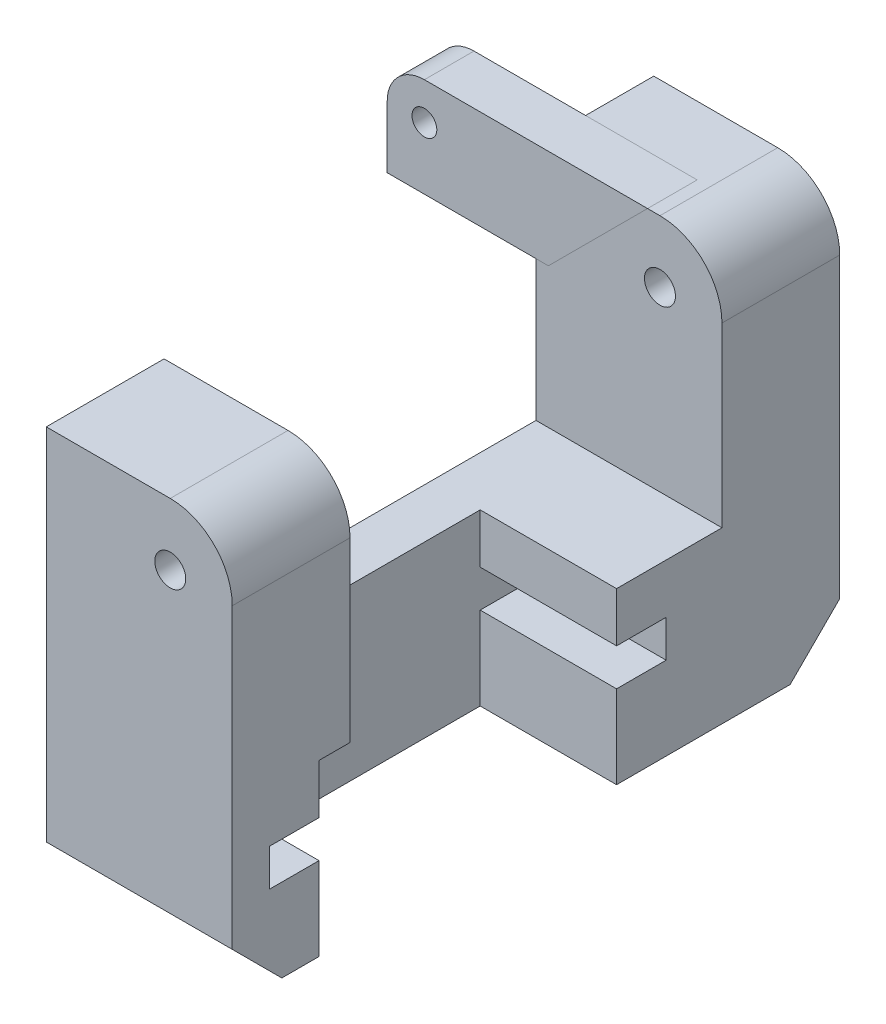
SolidWorks part; units mm, degrees
material "3D printed plastic"
ref_plane "Front Plane" through (0, 0, 0) normal (0, 0, 1) x (1, 0, 0)
ref_plane "Top Plane" through (0, 0, 0) normal (0, 1, 0) x (1, 0, 0)
ref_plane "Right Plane" through (0, 0, 0) normal (1, 0, 0) x (0, 0, -1)
sketch "Sketch1" plane through (0, 0, 0) normal (1, 0, 0) x (0, 0, -1)
  line L0 (0, 0) -> (0, -16.5) construction
  line L1 (-24.5, 16.5) -> (24.5, 16.5)
  line L2 (-24.5, 16.5) -> (-24.5, -16.5)
  line L3 (-24.5, -16.5) -> (24.5, -16.5)
  line L4 (24.5, 16.5) -> (24.5, -16.5)
  line L5 (0, 0) -> (0, 16.5) construction
  dimension "D1" = 49
  dimension "D2" = 33
extrude "Boss-Extrude1" add sketch "Sketch1" along normal mid plane 15
sketch "Sketch2" plane through (0, 0, 24.5) normal (0, 0, 1) x (1, 0, 0)
  line L0 (7.5, 16.5) -> (7.5, -16.5) construction
  line L1 (7.5, 16.5) -> (-7.5, 16.5) construction
  line L2 (2.5, 16.5) -> (7.5, 16.5)
  line L3 (7.5, 16.5) -> (7.5, 11.5)
  circle A0 centre (2.5, 11.5) radius 1.25
  arc A1 (7.5, 11.5) -> (2.5, 16.5) centre (2.5, 11.5) ccw
  dimension "D1" = 2.5
  dimension "D2" = 5
  dimension "D3" = 5
extrude "Cut-Extrude1" cut sketch "Sketch2" against normal through all
sketch "Sketch3" plane through (7.5, 0, 0) normal (1, 0, 0) x (0, 0, -1)
  line L0 (-24.5, -16.5) -> (24.5, -16.5) construction
  line L1 (-17.5, -16.5) -> (6.5, -16.5)
  line L2 (-17.5, -16.5) -> (-17.5, -9.8)
  line L3 (-17.5, -9.8) -> (6.5, -9.8)
  line L4 (6.5, -16.5) -> (6.5, -9.8)
  line L5 (-24.5, 11.5) -> (-24.5, -16.5) construction
  line L6 (24.5, 11.5) -> (-24.5, 11.5) construction
  dimension "D1" = 7
  dimension "D2" = 24
  dimension "D3" = 21.3
extrude "Cut-Extrude2" cut sketch "Sketch3" against normal blind 11
sketch "Sketch4" plane through (-3.5, 0, 0) normal (1, 0, 0) x (0, 0, -1)
  line L0 (6.5, -6.8) -> (10.5, -6.8)
  line L1 (-21.5, -9.8) -> (10.5, -9.8)
  line L2 (-21.5, -9.8) -> (-21.5, -6.8)
  line L3 (-21.5, -6.8) -> (-17.5, -6.8)
  line L4 (10.5, -9.8) -> (10.5, -6.8)
  line L5 (6.5, -9.8) -> (-17.5, -9.8) construction
  line L6 (-17.5, -6.8) -> (-17.5, -2.8)
  line L7 (-17.5, -2.8) -> (6.5, -2.8)
  line L8 (6.5, -6.8) -> (6.5, -2.8)
  line L9 (-5.5, -2.8) -> (-5.5, -16.5) construction
  line L10 (-17.5, -16.5) -> (6.5, -16.5) construction
  line L11 (6.5, -16.5) -> (6.5, -9.8) construction
  dimension "D1" = 3
  dimension "D2" = 32
  dimension "D3" = 4
extrude "Cut-Extrude3" cut sketch "Sketch4" along normal through all
sketch "Sketch5" plane through (0, 16.5, 0) normal (0, 1, 0) x (1, 0, 0)
  line L0 (7.5, 24.5) -> (7.5, -24.5) construction
  line L1 (7.5, 15) -> (-7.5, 15)
  line L2 (7.5, 15) -> (7.5, -15)
  line L3 (7.5, -15) -> (-7.5, -15)
  line L4 (-7.5, 15) -> (-7.5, -15)
  line L5 (-7.5, 24.5) -> (-7.5, -24.5) construction
  line L6 (0, 0) -> (7.5, 0) construction
  dimension "D1" = 30
extrude "Cut-Extrude4" cut sketch "Sketch5" against normal up to surface (19.3 mm away) up to face at (2, -2.8, 5.5)
sketch "Sketch6" plane through (0, 0, -15) normal (0, 0, 1) x (1, 0, 0)
  line L0 (2.5, 16.5) -> (-7.5, 16.5) construction
  line L1 (-2.5, 16.5) -> (-7.5, 16.5)
  line L2 (-2.5, 16.5) -> (-2.5, 8.5)
  line L3 (-2.5, 8.5) -> (-7.5, 8.5)
  line L4 (-7.5, 16.5) -> (-7.5, 8.5)
  line L5 (-7.5, -2.8) -> (-7.5, 16.5) construction
  dimension "D1" = 5
  dimension "D2" = 8
extrude "Cut-Extrude5" cut sketch "Sketch6" against normal blind 4
chamfer "Chamfer1" distance 4 angle 45 2 edges at (-2.5, 16.5, -17) (-2.5, 8.5, -17)
sketch "Sketch7" plane through (0, 0, -19) normal (0, 0, 1) x (1, 0, 0)
  line L1 (1.5, 16.5) -> (-19.5, 16.5)
  line L2 (1.5, 16.5) -> (-6.5, 8.5)
  line L3 (-6.5, 8.5) -> (-19.5, 8.5)
  line L4 (-19.5, 16.5) -> (-19.5, 8.5)
  line L5 (-7.5, 8.5) -> (-6.5, 8.5) construction
  line L6 (-7.5, 16.5) -> (-7.5, 8.5) construction
  line L7 (-6.5, 8.5) -> (-2.5, 12.5) construction
  circle A0 centre (-16.5, 13.5) radius 1
  dimension "D4" = 2
  dimension "D1" = 12
  dimension "D2" = 3
  dimension "D3" = 3
extrude "Boss-Extrude2" add sketch "Sketch7" along normal up to surface (4 mm away) separate body up to face at (-0.4956, 8.6794, -15)
fillet "Fillet1" radius 3 1 edges at (-19.5, 16.5, -17)
chamfer "Chamfer2" distance 4 angle 45 2 edges at (0, -16.5, -24.5) (0, -16.5, 24.5)
